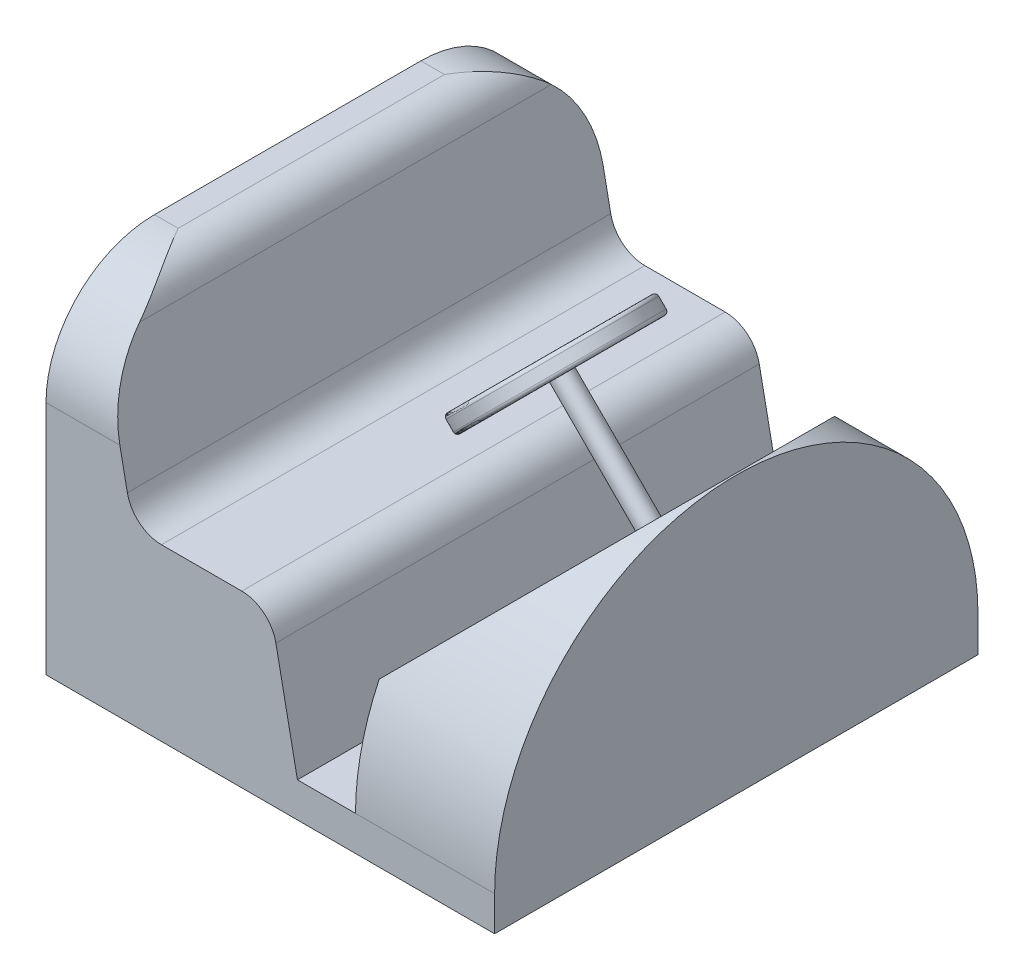
SolidWorks part; units mm, degrees
ref_plane "Front Plane" through (0, 0, 0) normal (0, 0, 1) x (1, 0, 0)
ref_plane "Top Plane" through (0, 0, 0) normal (0, 1, 0) x (1, 0, 0)
ref_plane "Right Plane" through (0, 0, 0) normal (1, 0, 0) x (0, 0, -1)
sketch "Sketch2" plane through (0, 0, 0) normal (0, 1, 0) x (1, 0, 0)
  line L1 (0, -17.653) -> (-32.766, -17.653)
  line L2 (0, -17.653) -> (0, 17.653)
  line L3 (0, 17.653) -> (-32.766, 17.653)
  line L4 (-32.766, -17.653) -> (-32.766, 17.653)
  point P4 (0, 0)
  dimension "D1" = 35.306
  dimension "D2" = 32.766
extrude "Boss-Extrude1" add sketch "Sketch2" along normal blind 2.54 contours L2 L1 L4 L3
sketch "Sketch3" plane through (0, 0, 0) normal (0, 0, 1) x (1, 0, 0)
  line L0 (-32.766, 2.54) -> (-32.766, 25.146)
  line L1 (-32.766, 25.146) -> (-28.956, 25.146)
  line L2 (-28.956, 25.146) -> (-26.416, 12.446)
  line L3 (-26.416, 12.446) -> (-16.383, 12.446)
  line L4 (-16.383, 12.446) -> (-14.4018, 2.54)
  line L5 (0, 2.54) -> (-32.766, 2.54) construction
  line L6 (-14.4018, 2.54) -> (-32.766, 2.54)
  dimension "D1" = 25.146
  dimension "D2" = 12.7
  dimension "D3" = 3.81
  dimension "D4" = 6.35
  dimension "D5" = 16.383
extrude "Boss-Extrude2" add sketch "Sketch3" along normal mid plane 35.306
fillet "Fillet1" radius 2.54 3 edges at (-16.383, 12.446, 0) (-26.416, 12.446, 0) (-28.956, 25.146, 0)
fillet "Fillet2" radius 7.9248 2 edges at (-31.9022, 25.146, 17.653) (-29.428, 24.5703, 17.653)
fillet "Fillet3" radius 7.9248 2 edges at (-31.9022, 25.146, -17.653) (-29.428, 24.5703, -17.653)
sketch "Sketch10" plane through (0, 0, 0) normal (0, 0, 1) x (1, 0, 0)
  line L0 (0, 2.54) -> (0, 20.32)
  line L1 (0, 20.32) -> (-10.16, 10.16)
  line L3 (-10.16, 2.54) -> (0, 2.54)
  line L4 (-10.16, 10.16) -> (-10.16, 2.54)
  dimension "D1" = 20.32
  dimension "D2" = 10.16
  dimension "D3" = 7.62
extrude "Boss-Extrude3" add sketch "Sketch10" along normal mid plane 35.306
sketch "Sketch11" plane through (0, 0, 0) normal (1, 0, 0) x (0, 0, -1)
  line L1 (-17.653, 20.32) -> (-17.653, 0) construction
  line L3 (-17.653, 2.54) -> (-17.653, 20.32)
  line L4 (-17.653, 20.32) -> (17.653, 20.32)
  line L5 (17.653, 20.32) -> (17.653, 2.54)
  arc A0 (-17.653, 2.54) -> (17.653, 2.54) centre (0, 2.54) cw
  dimension "D1" = 17.78
extrude "Cut-Extrude2" cut sketch "Sketch11" against normal up to surface (10.16 mm away) up to face at (-10.16, 6.35, 0)
sketch "Sketch12" plane through (-10.16, 10.16, 0) normal (-0.7071, 0.7071, 0) x (0, 0, 1)
  circle A0 centre (0, 5.2798) radius 0.762
  dimension "D1" = 1.524
  dimension "D2" = 17.653
  dimension "D3" = 10.668
extrude "Boss-Extrude4" add sketch "Sketch12" along normal blind 10.16
sketch "Sketch13" plane through (-17.3442, 17.3442, 0) normal (-0.7071, 0.7071, 0) x (0.7071, 0.7071, 0)
  line L0 (4.8988, 0.6599) -> (4.8988, 5.7023)
  line L1 (5.6608, 0.6599) -> (5.6608, 5.7023)
  line L2 (5.9398, 0.381) -> (10.9821, 0.381)
  line L3 (5.9398, -0.381) -> (10.9821, -0.381)
  line L4 (5.6608, -0.6599) -> (5.6608, -5.7023)
  line L5 (4.8988, -0.6599) -> (4.8988, -5.7023)
  line L6 (4.6199, -0.381) -> (-0.4224, -0.381)
  line L7 (4.6199, 0.381) -> (-0.4224, 0.381)
  circle A0 centre (5.2798, 0) radius 6.35
  arc A1 (4.8988, 5.7023) -> (-0.4224, 0.381) centre (5.2798, 0) ccw
  arc A2 (4.8988, 0.6599) -> (4.6199, 0.381) centre (5.2798, 0) ccw
  arc A3 (5.6608, -0.6599) -> (5.9398, -0.381) centre (5.2798, 0) ccw
  arc A4 (4.6199, -0.381) -> (4.8988, -0.6599) centre (5.2798, 0) ccw
  arc A5 (5.9398, 0.381) -> (5.6608, 0.6599) centre (5.2798, 0) ccw
  arc A6 (5.6608, -5.7023) -> (10.9821, -0.381) centre (5.2798, 0) ccw
  arc A7 (-0.4224, -0.381) -> (4.8988, -5.7023) centre (5.2798, 0) ccw
  arc A8 (10.9821, 0.381) -> (5.6608, 5.7023) centre (5.2798, 0) ccw
  dimension "D1" = 12.7
  dimension "D2" = 11.43
  dimension "D3" = 1.524
  dimension "D4" = 0.762
  dimension "D5" = 4
extrude "Boss-Extrude5" add sketch "Sketch13" against normal blind 1.27 separate body contours A0 A1
fillet "Fillet4" radius 0.254 26 edges at (-9.8553, 23.0371, 4.0411) (-17.2029, 15.6895, 0) (-9.8553, 23.0371, -4.0411) (-15.5703, 17.3221, -4.0411) (-15.5703, 17.3221, 4.0411) (-10.7533, 23.9351, 4.0411) (-16.4683, 18.2201, 4.0411) (-18.1009, 16.5875, 0) (-16.4683, 18.2201, -4.0411) (-10.7533, 23.9351, -4.0411) (-12.9822, 19.9102, -3.1811) (-12.9822, 19.9102, 3.1811) (-14.9621, 17.9302, -0.381) (-10.4634, 22.429, -0.381) (-14.9621, 17.9302, 0.381) (-10.4634, 22.429, 0.381) (-12.4434, 20.449, 3.1811) (-12.4434, 20.449, -3.1811) (-11.3614, 23.327, -0.381) (-11.3614, 23.327, 0.381) (-13.3414, 21.347, 3.1811) (-13.8802, 20.8082, 3.1811) (-15.8602, 18.8282, 0.381) (-15.8602, 18.8282, -0.381) (-13.3414, 21.347, -3.1811) (-13.8802, 20.8082, -3.1811)
